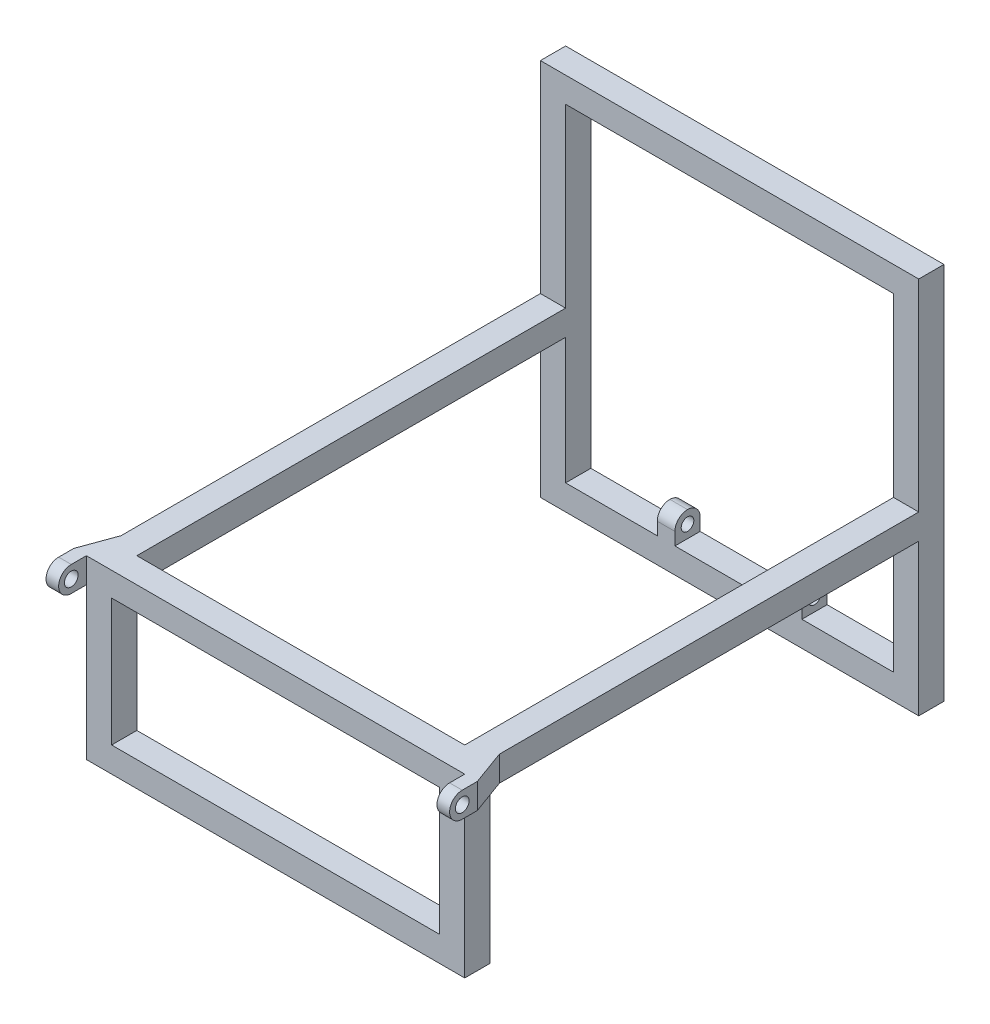
SolidWorks part; units mm, degrees
ref_plane "Alzado" through (0, 0, 0) normal (0, 0, 1) x (1, 0, 0)
ref_plane "Planta" through (0, 0, 0) normal (0, 1, 0) x (1, 0, 0)
ref_plane "Vista lateral" through (0, 0, 0) normal (1, 0, 0) x (0, 0, -1)
sketch "Croquis1" plane through (0, 0, 0) normal (1, 0, 0) x (0, 0, -1)
  line L0 (-100, 700) -> (-100, 1500)
  line L1 (0, 0) -> (-100, 0)
  line L2 (0, 0) -> (0, 1500)
  line L3 (0, 1500) -> (-100, 1500)
  line L4 (-100, 0) -> (-100, 600)
  line L5 (-100, 600) -> (-1800, 600)
  line L6 (0, 600) -> (0, 700)
  line L7 (-100, 700) -> (-1900, 700)
  line L8 (-1900, 600) -> (-1900, 700)
  line L10 (-1900, 600) -> (-1900, 0)
  line L11 (-1900, 0) -> (-1800, 0)
  line L12 (-1800, 600) -> (-1800, 0)
  point P16 (-950, 600)
  point P17 (-50, 0)
  point P18 (-1850, 0)
  dimension "D1" = 100
  dimension "D2" = 1500
  dimension "D3" = 700
  dimension "D4" = 100
  dimension "D5" = 1700
  dimension "D6" = 600
extrude "Saliente-Extruir1" add sketch "Croquis1" against normal mid plane 1500 contours L7 L8 L10 L11 L12 L5 L4 L1 L2 L3 L0
sketch "Croquis3" plane through (0, 0, 0) normal (0, 0, -1) x (-1, 0, 0)
  line L0 (750, 0) -> (750, 1500) construction
  line L1 (750, 0) -> (-750, 0) construction
  line L2 (750, 1500) -> (-750, 1500) construction
  line L8 (-750, 0) -> (-750, 1500) construction
  line L9 (-650, 1400) -> (650, 1400)
  line L10 (-650, 1400) -> (-650, 100)
  line L11 (-650, 100) -> (650, 100)
  line L12 (650, 1400) -> (650, 100)
  dimension "D1" = 100
  dimension "D2" = 100
  dimension "D3" = 100
  dimension "D4" = 100
extrude "Cortar-Extruir4" cut sketch "Croquis3" against normal up to surface (1800 mm away) up to face at (0, 300, 1800)
sketch "Croquis4" plane through (0, 0, 1900) normal (0, 0, 1) x (1, 0, 0)
  line L0 (-750, 700) -> (750, 700) construction
  line L1 (-650, 604.6492) -> (650, 604.6492)
  line L2 (-650, 604.6492) -> (-650, 100)
  line L3 (-650, 100) -> (650, 100)
  line L4 (650, 604.6492) -> (650, 100)
  line L5 (750, 0) -> (750, 700) construction
  line L6 (-750, 0) -> (750, 0) construction
  line L7 (-750, 700) -> (-750, 0) construction
  dimension "D1" = 95.3508
  dimension "D2" = 100
  dimension "D3" = 100
  dimension "D4" = 100
extrude "Cortar-Extruir5" cut sketch "Croquis4" against normal up to next
sketch "Croquis5" plane through (750, 0, 0) normal (1, 0, 0) x (0, 0, -1)
  line L0 (-1960, 600) -> (-1900, 600)
  line L1 (-1900, 0) -> (-1900, 700) construction
  line L2 (-1900, 600) -> (-1900, 700)
  line L4 (-1900, 700) -> (-1960, 700)
  arc A0 (-1960, 700) -> (-1960, 600) centre (-1960, 650) ccw
  circle A1 centre (-1960, 650) radius 27.1847
  dimension "D1" = 60
  dimension "D2" = 100
  dimension "D3" = 54.3694
extrude "Saliente-Extruir2" add sketch "Croquis5" along normal blind 50 separate body
sketch "Croquis6" plane through (0, 700, 0) normal (0, 1, 0) x (1, 0, 0)
  line L0 (750, -1900) -> (800, -1900)
  line L1 (800, -1900) -> (750, -1762.6261)
  line L2 (750, -100) -> (750, -1900) construction
  line L3 (750, -1900) -> (750, -1762.6261)
  dimension "D1" = 70
extrude "Saliente-Extruir3" add sketch "Croquis6" against normal up to surface (100 mm away) up to face at (775, 600, 1930)
sketch "Croquis8" plane through (-750, 0, 0) normal (-1, 0, 0) x (0, 0, 1)
  line L0 (1900, 700) -> (1960, 700)
  line L1 (1900, 600) -> (1960, 600)
  line L2 (1900, 700) -> (1960, 700) construction
  line L3 (1900, 700) -> (1960, 700) construction
  circle A0 centre (1960, 650) radius 27.1845
  arc A1 (1960, 600) -> (1960, 700) centre (1960, 650) ccw
  line M11 (1900, 0) -> (1900, 700)
  dimension "D1" = 54.369
extrude "Saliente-Extruir4" add sketch "Croquis8" along normal blind 50 separate body contours L1 A1 L0 A0 M11 region at (-750, 698.5134, 1930)
sketch "Croquis9" plane through (0, 700, 0) normal (0, 1, 0) x (1, 0, 0)
  line L0 (-750, -1900) -> (-800, -1900)
  line L1 (-800, -1900) -> (-750, -1762.6261)
  line L2 (-750, -100) -> (-750, -1900) construction
  line L3 (-750, -1762.6261) -> (-750, -1900)
  dimension "D1" = 70
extrude "Saliente-Extruir5" add sketch "Croquis9" against normal up to surface (100 mm away) up to face at (-775, 600, 1930)
sketch "Croquis11" plane through (0, 0, 0) normal (0, 0, -1) x (-1, 0, 0)
  line L0 (-650, 100) -> (650, 100) construction
  line L1 (-286.7, 100) -> (-216.7, 100)
  line L2 (-286.7, 100) -> (-286.7, 200)
  line L3 (-286.7, 200) -> (-216.7, 200)
  line L4 (-216.7, 100) -> (-216.7, 200)
  line L5 (-216.7, 700) -> (-216.7, 800) construction
  line L6 (0, 0) -> (0, 100) construction
  line L7 (286.7, 200) -> (216.7, 200)
  line L8 (216.7, 100) -> (216.7, 200)
  line L9 (286.7, 100) -> (216.7, 100)
  line L10 (286.7, 100) -> (286.7, 200)
  point P8 (-216.7, 750)
  point P9 (-216.7, 150)
  dimension "D1" = 70
  dimension "D2" = 100
extrude "Saliente-Extruir6" add sketch "Croquis11" against normal up to surface (100 mm away) up to face at (0, 325, 100)
fillet "Redondeo1" radius 50 4 edges at (251.7, 200, 100) (251.7, 200, 0) (-251.7, 200, 0) (-251.7, 200, 100)
sketch "Croquis12" plane through (-286.7, 0, 0) normal (-1, 0, 0) x (0, 0, 1)
  circle A0 centre (50, 150) radius 25
  arc A1 (100, 150) -> (50, 200) centre (50, 150) ccw construction
  dimension "D1" = 50
extrude "Cortar-Extruir6" cut sketch "Croquis12" against normal up to surface (573.4 mm away) up to face at (286.7, 144.1421, 50)
